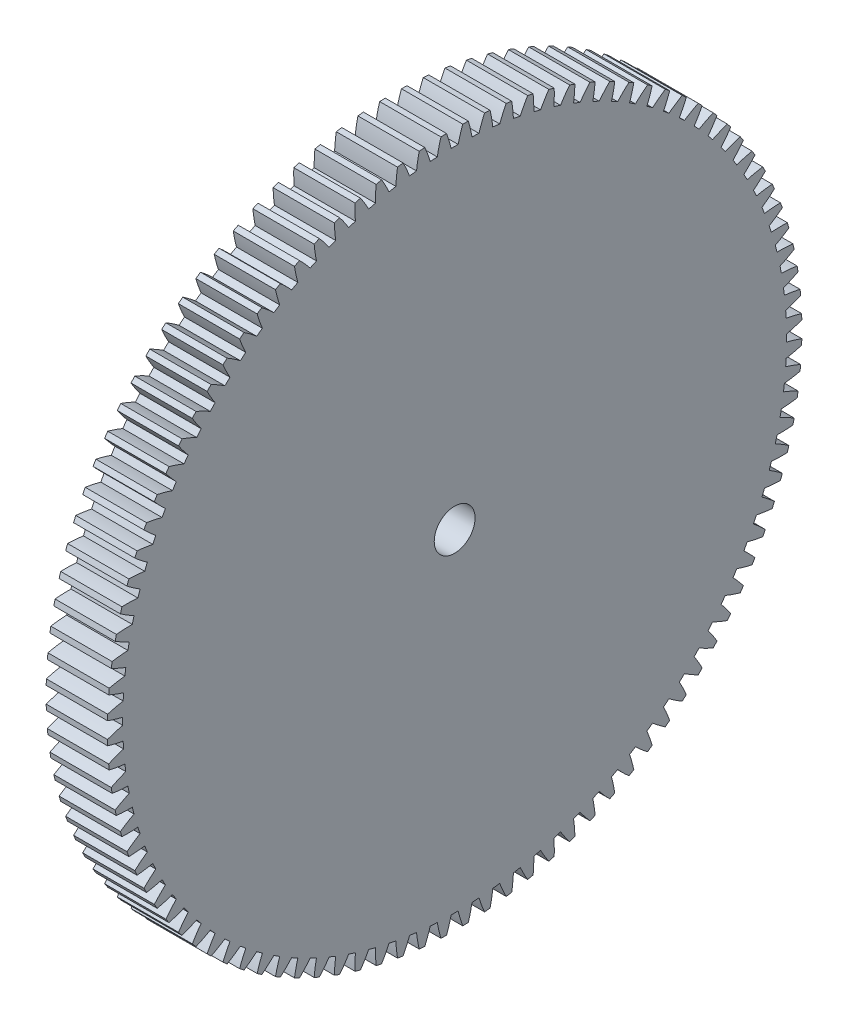
SolidWorks part; units mm, degrees
ref_plane "Plane1" through (0, 0, 0) normal (0, 0, 1) x (1, 0, 0)
ref_plane "Plane2" through (0, 0, 0) normal (0, 1, 0) x (1, 0, 0)
ref_plane "Plane3" through (0, 0, 0) normal (1, 0, 0) x (0, 0, -1)
sketch "HoldingSke" plane through (0, 0, 0) normal (0, 1, 0) x (1, 0, 0)
  line L0 (0, 0) -> (-52.928, -300.1694)
  line L1 (-15, 0) -> (100, 0) construction
  line L2 (0, 0) -> (-2.1039, 2.3779)
  line L3 (0, 0) -> (-11.863, 4.5341)
  line L4 (0, 0) -> (-1.4996, 8.5048)
  line L5 (0, 0) -> (-47.5972, -17.7524)
  line L6 (0, 0) -> (-15.7917, -10.6547)
  line L7 (-2.1039, 2.3779) -> (8.8308, 51.9871)
  line L8 (-76.2, 54.61) -> (-61.976, 54.61)
  line L9 (-67.7845, 28.3722) -> (-49.3413, 33.142)
  line L10 (-76.2, 71.12) -> (104.1128, 71.12)
  line L11 (0, 0) -> (-19.05, 0)
  line L12 (-76.2, 101.6) -> (-76.1147, 101.6)
  line L13 (24.9733, 27.94) -> (52.9518, 28.4284)
  line L14 (24.9733, 27.94) -> (24.9746, 27.94)
  line L15 (24.9733, 27.94) -> (100.4006, 29.5858)
  circle A0 centre (0, 0) radius 6.35
  circle A1 centre (0, 0) radius 38.1
  circle A2 centre (0, 0) radius 38.1
  circle A3 centre (0, 0) radius 6.35
  dimension "Num_teeth" = 100
  dimension "H" = 19.05
  dimension "Pitch_radius" = 180.3128
  dimension "Width" = 19.05
  dimension "Thickness" = 19.05
sketch "BasProSke" plane through (0, 0, 0) normal (0, 1, 0) x (1, 0, 0)
  line L0 (-10, 0) -> (60, 0) construction
  line L1 (0, 0) -> (0, 107.95)
  line L2 (0, 0) -> (19.05, 0)
  line L3 (19.05, 0) -> (19.05, 107.95)
  line L4 (19.05, 107.95) -> (0, 107.95)
  dimension "Thickness" = 19.05
  dimension "Diameter" = 215.9
revolve "Base-Revolve" add sketch "BasProSke" angle 360 about L0
sketch "TooCutSke" plane through (0, 0, 0) normal (1, 0, 0) x (0, 0, -1)
  line L1 (0, 0) -> (0, 107) construction
  line L2 (0, 0) -> (-1.8117, 105.8178) construction
  line L3 (0, 0) -> (-6.6479, 211.5406) construction
  line L4 (-1.8117, 105.8178) -> (-3.324, 105.7703) construction
  arc A0 (1.0906, 103.1805) -> (-1.0906, 103.1805) centre (0, 0) ccw
  arc A1 (2.5305, 107.9457) -> (-2.5305, 107.9457) centre (0, 0) ccw
  circle A2 centre (0, 0) radius 105.8333 construction
  circle A3 centre (0, 0) radius 102.4623 construction
  arc A4 (-1.0906, 103.1805) -> (-2.5305, 107.9457) centre (-42.2642, 93.3395) ccw
  arc A5 (2.5305, 107.9457) -> (1.0906, 103.1805) centre (42.2642, 93.3395) ccw
extrude "ToothCut" cut sketch "TooCutSke" along normal through all
fillet "Breaks" [suppressed] radius 0.0423 tangent propagation no
fillet "RootFillets" [suppressed] radius 0.5304
pattern_circular "TeethCuts" count 100 every 3.6 about axis through (-10, 0, 0) along (1, 0, 0) of "ToothCut", "RootFillets", "Breaks"
sketch "HubNeaOneSke" plane through (0, 0, 0) normal (-1, 0, 0) x (0, 0, 1)
  circle A0 centre (0, 0) radius 38.1
  dimension "Diameter" = 76.2
extrude "HubNearOne" [suppressed] add sketch "HubNeaOneSke" along normal blind 31.7501
sketch "HubNeaBotSke" plane through (0, 0, 0) normal (-1, 0, 0) x (0, 0, 1)
  circle A0 centre (0, 0) radius 38.1
  dimension "Diameter" = 76.2
extrude "HubNearBoth" [suppressed] add sketch "HubNeaBotSke" along normal blind 15.875
ref_plane "FarPln" through (19.05, 0, 0) normal (1, 0, 0) x (0, 0, -1)
sketch "HubFarSke" plane through (19.05, 0, 0) normal (1, 0, 0) x (0, 0, -1)
  circle A0 centre (0, 0) radius 38.1
  dimension "Diameter" = 76.2
extrude "HubFar" [suppressed] add sketch "HubFarSke" along normal blind 15.875
sketch "BorSke" plane through (0, 0, 0) normal (1, 0, 0) x (0, 0, -1)
  circle A0 centre (0, 0) radius 6.35
  dimension "Diameter" = 12.7
extrude "Bore" cut sketch "BorSke" along normal mid plane 101.6001
sketch "KeySke" plane through (0, 0, 0) normal (1, 0, 0) x (0, 0, -1)
  line L0 (-1.5875, 0) -> (-1.5875, 7.874)
  line L1 (-1.5875, 7.874) -> (1.5875, 7.874)
  line L2 (1.5875, 7.874) -> (1.5875, 0)
  line L3 (0, 0) -> (0, 34) construction
  line L4 (-1.5875, 0) -> (1.5875, 0)
  dimension "Width" = 3.175
extrude "Keyway" [suppressed] cut sketch "KeySke" along normal mid plane 101.6001
pattern_circular "Keyway2" [suppressed] count 2 every 90 about axis through (-10, 0, 0) along (1, 0, 0) reverse direction yes
equation "' \"Pitch@HoldingSke\" = 4"
equation "' \"Num_teeth@HoldingSke\" = 12"
equation "' \"Ap@HoldingSke\" =  20"
equation "' \"Ap@HoldingSke\" = 20"
equation "' \"Width@HoldingSke\" = 0.5"
equation "' \"Hub_dia@HoldingSke\"= 1"
equation "' \"Hub_dia@HoldingSke\" = 1"
equation "' \"Overall_len@HoldingSke\" = 1.0"
equation "' \"Bore@HoldingSke\" = 0.75"
equation "' \"T_dim@HoldingSke\" = 0.85"
equation "' \"Width@KeySke\" = 0.25"
equation "' \"Show_teeth@HoldingSke\" = 13"
equation "' \"Backlash@HoldingSke\" = 0.009"
equation "' \"Addendum_fac@HoldingSke\" = 1.0"
equation "' \"Dedendum_fac@HoldingSke\" = 1.25"
equation "' \"Dedendum_add@HoldingSke\" = 0.00005"
equation "' \"Clearance_fac@HoldingSke\" = 0.25"
equation "' \"Pitch@HoldingSke\" = 0.5"
equation "' \"Num_teeth@HoldingSke\" = 23"
equation "' \"Show_teeth@HoldingSke\" = 23"
equation "' \"Backlash@HoldingSke\" = 0.0375"
equation "\"Overcut_dia@TooCutSke\" = (\"Num_teeth@HoldingSke\" + 2 * \"Addendum_fac@HoldingSke\") / \"Pitch@HoldingSke\" + 0.002"
equation "\"Pitch_dia@TooCutSke\" = \"Num_teeth@HoldingSke\" / \"Pitch@HoldingSke\""
equation "\"Base_dia@TooCutSke\" = \"Num_teeth@HoldingSke\" / \"Pitch@HoldingSke\" * cos((\"Ap@HoldingSke\"  * 3.14159265 / 180))"
equation "\"Root_dia@TooCutSke\" = (\"Num_teeth@HoldingSke\" + 2) / \"Pitch@HoldingSke\" - 2 * (\"Addendum_fac@HoldingSke\" + \"Dedendum_fac@HoldingSke\") / \"Pitch@HoldingSke\" - \"Dedendum_add@HoldingSke\" * 2"
equation "\"Half_ang@TooCutSke\" = 180 / \"Num_teeth@HoldingSke\""
equation "\"Half_CT@TooCutSke\" = \"Num_teeth@HoldingSke\" / \"Pitch@HoldingSke\" * sin((3.14159265 / 2 / \"Num_teeth@HoldingSke\")) / 2 - 7 * \"Backlash@HoldingSke\" / 4"
equation "\"Flank_rad@TooCutSke\" = \"Num_teeth@HoldingSke\" / \"Pitch@HoldingSke\" / 5"
equation "\"Radius@RootFillets\" = \"Clearance_fac@HoldingSke\" / \"Pitch@HoldingSke\" + \"Dedendum_add@HoldingSke\""
equation "\"Break_rad@Breaks\" = 0.02 / \"Pitch@HoldingSke\""
equation "\"Thickness@HoldingSke\" = \"Width@HoldingSke\""
equation "\"OAL@HoldingSke\" = \"Thickness@HoldingSke\""
equation "\"MHD@HoldingSke\" = (\"Num_teeth@HoldingSke\" + 2) / \"Pitch@HoldingSke\" - 2 * (\"Addendum_fac@HoldingSke\" + \"Dedendum_fac@HoldingSke\")  / \"Pitch@HoldingSke\" - \"Dedendum_add@HoldingSke\" * 2"
equation "\"MBD@HoldingSke\" = (\"Num_teeth@HoldingSke\" + 2) / \"Pitch@HoldingSke\" - 2 * (\"Addendum_fac@HoldingSke\" + \"Dedendum_fac@HoldingSke\")  / \"Pitch@HoldingSke\" - \"Dedendum_add@HoldingSke\" * 2 - 0.002"
equation "\"MHD@HoldingSke\" = ((sgn( \"MHD@HoldingSke\" - \"Hub_dia@HoldingSke\" )-1)*( \"MHD@HoldingSke\" - \"Hub_dia@HoldingSke\" ))/-2+ \"Hub_dia@HoldingSke\""
equation "\"MBD@HoldingSke\" = ((sgn( \"MBD@HoldingSke\" - \"Bore@HoldingSke\" )-1)*( \"MBD@HoldingSke\" - \"Bore@HoldingSke\" ))/-2+ \"Bore@HoldingSke\""
equation "\"OAL@HoldingSke\" = ((sgn( \"OAL@HoldingSke\" - \"Overall_len@HoldingSke\" )+1)*( \"OAL@HoldingSke\" - \"Overall_len@HoldingSke\" ))/2 + \"Overall_len@HoldingSke\" + 0.000002"
equation "\"Num_teeth@TeethCuts\" = int( \"Show_teeth@HoldingSke\" ) + 1"
equation "\"Num_teeth@TeethCuts\" = ((sgn( \"Num_teeth@TeethCuts\" - \"Num_teeth@HoldingSke\" )-1)*( \"Num_teeth@TeethCuts\" - \"Num_teeth@HoldingSke\" ))/-2+ \"Num_teeth@HoldingSke\""
equation "\"Num_teeth@TeethCuts\" = ((sgn( \"Num_teeth@TeethCuts\" - 2.0)+1)*( \"Num_teeth@TeethCuts\" - 2.0))/2 +2.0"
equation "\"Angle@TeethCuts\" = 360.0 / \"Num_teeth@HoldingSke\""
equation "\"Diameter@BasProSke\" = (\"Num_teeth@HoldingSke\" + 2 * \"Addendum_fac@HoldingSke\") / \"Pitch@HoldingSke\""
equation "\"Thickness@BasProSke\"  = \"Thickness@HoldingSke\""
equation "' \"Fillet_rad@BasProSke\" =  \"Thickness@HoldingSke\" * 0.05"
equation "' \"Fillet_rad@BasProSke\" = \"Thickness@HoldingSke\" * 0.05"
equation "\"MHD@HoldingSke\" = ((sgn( \"MHD@HoldingSke\" - \"Root_dia@TooCutSke\" )-1)*( \"MHD@HoldingSke\" - \"Root_dia@TooCutSke\" ))/-2+ \"Root_dia@TooCutSke\""
equation "\"Diameter@HubNeaOneSke\" = \"MHD@HoldingSke\""
equation "\"Length@HubNearOne\" = \"OAL@HoldingSke\" - \"Thickness@BasProSke\""
equation "\"Diameter@HubNeaBotSke\" = \"MHD@HoldingSke\""
equation "\"Length@HubNearBoth\" = ( \"OAL@HoldingSke\" - \"Thickness@BasProSke\" ) / 2.0"
equation "\"Thickness@FarPln\" = \"Thickness@BasProSke\""
equation "\"Diameter@HubFarSke\" = \"MHD@HoldingSke\""
equation "\"Length@HubFar\" = ( \"OAL@HoldingSke\" - \"Thickness@BasProSke\" ) / 2.0"
equation "\"Diameter@BorSke\" = \"MBD@HoldingSke\""
equation "\"D1@Bore\" = \"OAL@HoldingSke\" * 2.0"
equation "\"D1@Keyway\" = \"OAL@HoldingSke\" * 2.0"
equation "\"Offset@KeySke\" = \"T_dim@HoldingSke\" - \"MBD@HoldingSke\" / 2.0"
